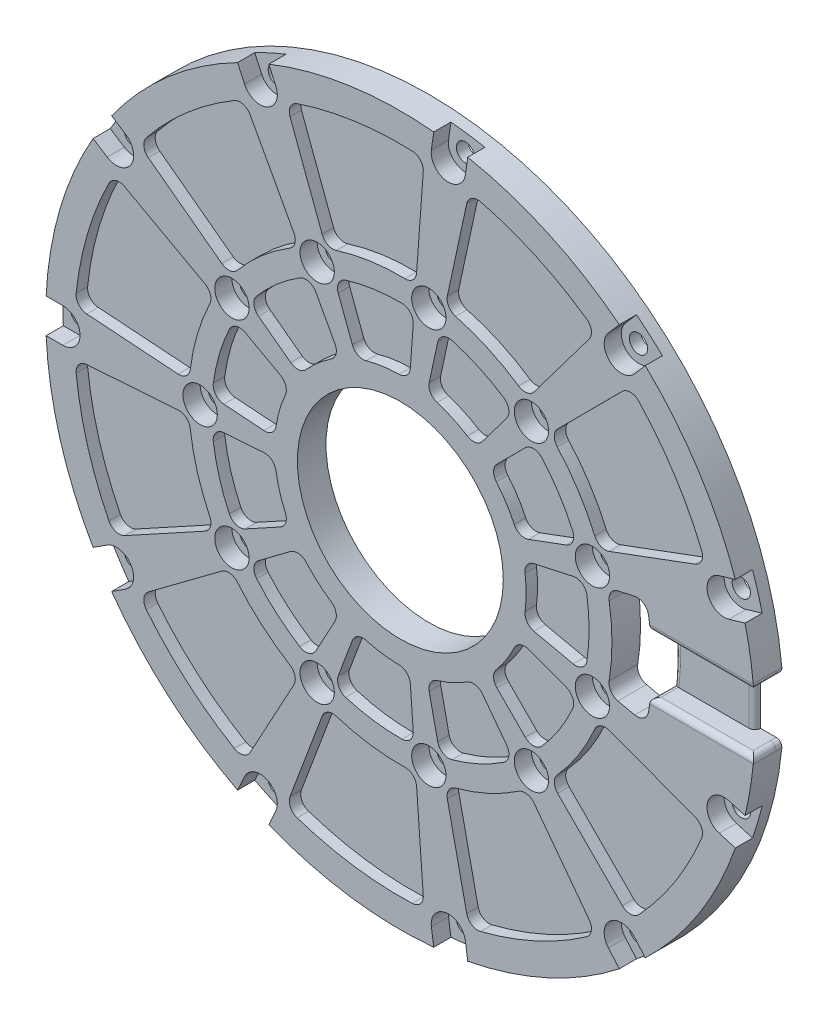
SolidWorks part; units mm, degrees
material "ABS"
ref_plane "Front Plane" through (0, 0, 0) normal (0, 0, 1) x (1, 0, 0)
ref_plane "Top Plane" through (0, 0, 0) normal (0, 1, 0) x (1, 0, 0)
ref_plane "Right Plane" through (0, 0, 0) normal (1, 0, 0) x (0, 0, -1)
sketch "Sketch1" plane through (0, 0, -63.9958) normal (0, 0, 1) x (1, 0, 0)
  circle A0 centre (89.0728, 47.2587) radius 62
  circle A2 centre (89.0728, 47.2587) radius 18
  dimension "D1" = 124
  dimension "D2" = 36
extrude "Boss-Extrude1" add sketch "Sketch1" along normal blind 5
sketch "Sketch2" plane through (0, 0, -58.9958) normal (0, 0, 1) x (1, 0, 0)
  line L0 (89.0728, 47.2587) -> (54.0728, 47.2587) construction
  circle A0 centre (54.0728, 47.2587) radius 1.575
  circle A1 centre (59.6289, 66.1811) radius 1.575
  circle A2 centre (74.5333, 79.0958) radius 1.575
  circle A3 centre (94.0538, 81.9025) radius 1.575
  circle A4 centre (111.9929, 73.7099) radius 1.575
  circle A5 centre (122.655, 57.1193) radius 1.575
  circle A6 centre (122.655, 37.3981) radius 1.575
  circle A7 centre (111.9929, 20.8075) radius 1.575
  circle A8 centre (94.0538, 12.615) radius 1.575
  circle A9 centre (74.5333, 15.4216) radius 1.575
  circle A10 centre (59.6289, 28.3363) radius 1.575
  point P27 (89.0728, 47.2587)
  dimension "D2" = 3.15
  dimension "D3" = 11
  dimension "D1" = 35
extrude "Cut-Extrude1" cut sketch "Sketch2" against normal through all
sketch "Sketch4" plane through (0, 0, -58.9958) normal (0, 0, 1) x (1, 0, 0)
  line L0 (89.0728, 47.2587) -> (30.0728, 47.2587) construction
  circle A0 centre (30.0728, 47.2587) radius 1.6
  circle A1 centre (39.4388, 79.1565) radius 1.6
  circle A2 centre (64.5633, 100.927) radius 1.6
  circle A3 centre (97.4694, 105.6582) radius 1.6
  circle A4 centre (127.7096, 91.8479) radius 1.6
  circle A5 centre (145.6829, 63.8809) radius 1.6
  circle A6 centre (145.6829, 30.6365) radius 1.6
  circle A7 centre (127.7096, 2.6695) radius 1.6
  circle A8 centre (97.4694, -11.1408) radius 1.6
  circle A9 centre (64.5633, -6.4096) radius 1.6
  circle A10 centre (39.4388, 15.3609) radius 1.6
  point P28 (89.0728, 47.2587)
  dimension "D2" = 3.2
  dimension "D1" = 59
  dimension "D3" = 11
extrude "Cut-Extrude3" cut sketch "Sketch4" against normal through all
sketch "Sketch3" plane through (0, 0, -58.9958) normal (0, 0, 1) x (1, 0, 0)
  line L0 (89.0728, 47.2587) -> (94.0538, 81.9025) construction
  line L1 (89.0728, 47.2587) -> (74.5333, 79.0958) construction
  line L2 (78.216, 76.2264) -> (80.6793, 69.654)
  line L3 (91.3287, 78.1118) -> (90.8168, 71.1116)
  line L44 (89.0728, 47.2587) -> (64.5633, 100.927) construction
  line L45 (89.0728, 47.2587) -> (97.4694, 105.6582) construction
  line L46 (75.4037, 83.73) -> (69.7833, 98.7263)
  line L47 (93.0808, 102.076) -> (91.913, 86.1037)
  line L52 (127.1182, 55.5982) -> (130.0522, 56.2414)
  line L53 (130.0522, 38.2761) -> (127.1182, 38.9192)
  line L68 (122.081, 91.207) -> (112.4633, 78.4017)
  line L69 (97.2915, 85.3304) -> (100.6709, 100.9847)
  line L70 (140.6014, 66.3848) -> (125.5873, 60.812)
  line L71 (116.5699, 74.8433) -> (127.8762, 86.1855)
  line L72 (142.7617, 35.4901) -> (127.1182, 38.9192) [skipped]
  line L73 (127.1182, 55.5982) -> (142.7617, 59.0273) [skipped]
  line L74 (127.8762, 8.3319) -> (116.5699, 19.6742)
  line L75 (125.5873, 33.7055) -> (140.6014, 28.1326)
  line L76 (100.6709, -6.4673) -> (97.2915, 9.187)
  line L77 (112.4633, 16.1158) -> (122.081, 3.3104)
  line L78 (69.7833, -4.2089) -> (75.4037, 10.7874)
  line L79 (91.913, 8.4137) -> (93.0808, -7.5586)
  line L80 (45.0199, 14.3901) -> (57.8558, 23.9671)
  line L81 (70.4609, 13.0447) -> (62.8081, -1.0234)
  line L82 (34.2431, 43.4246) -> (50.219, 44.5418)
  line L83 (54.918, 28.5384) -> (40.8742, 20.8409)
  line L84 (40.8742, 73.6765) -> (54.918, 65.979)
  line L85 (50.219, 49.9756) -> (34.2431, 51.0928)
  line L86 (62.8081, 95.5409) -> (70.4609, 81.4727)
  line L87 (57.8558, 70.5503) -> (45.0199, 80.1273)
  line L88 (95.6006, 77.4975) -> (94.1195, 70.6367)
  line L89 (107.651, 71.9943) -> (103.4358, 66.3821)
  line L90 (110.9127, 69.168) -> (105.9575, 64.1971)
  line L91 (118.0748, 58.0235) -> (111.4946, 55.5811)
  line L92 (119.2908, 53.8825) -> (112.4347, 52.3796)
  line L93 (119.2908, 40.635) -> (112.4347, 42.1378)
  line L94 (118.0748, 36.4939) -> (111.4946, 38.9363)
  line L95 (110.9127, 25.3494) -> (105.9575, 30.3204)
  line L96 (107.651, 22.5231) -> (103.4358, 28.1353)
  line L97 (95.6006, 17.0199) -> (94.1195, 23.8807)
  line L98 (91.3287, 16.4057) -> (90.8168, 23.4059)
  line L99 (78.216, 18.291) -> (80.6793, 24.8634)
  line L100 (74.2901, 20.0839) -> (77.6441, 26.2495)
  line L101 (64.2783, 28.7591) -> (69.9039, 32.9565)
  line L102 (61.945, 32.3899) -> (68.1, 35.7634)
  line L103 (58.2127, 45.1008) -> (65.2145, 45.5904)
  line L104 (58.2127, 49.4167) -> (65.2145, 48.927)
  line L105 (61.945, 62.1275) -> (68.1, 58.754)
  line L106 (64.2783, 65.7583) -> (69.9039, 61.5609)
  line L107 (74.2901, 74.4336) -> (77.6441, 68.2679)
  arc A0 (88.843, 69.2575) -> (83.0955, 68.4311) centre (89.0728, 47.2587) ccw
  arc A1 (89.3508, 80.2575) -> (79.5092, 78.8425) centre (89.0728, 47.2587) ccw
  arc A22 (91.3287, 78.1118) -> (89.3508, 80.2575) centre (89.334, 78.2576) ccw
  arc A23 (78.216, 76.2264) -> (79.5092, 78.8425) centre (80.0888, 76.9283) cw
  arc A24 (80.6793, 69.654) -> (83.0955, 68.4311) centre (82.5521, 70.3559) ccw
  arc A25 (90.8168, 71.1116) -> (88.843, 69.2575) centre (88.8222, 71.2574) cw
  arc A86 (77.8815, 82.5256) -> (89.875, 84.25) centre (89.0728, 47.2587) cw
  arc A87 (71.0227, 101.3253) -> (91.1594, 104.2205) centre (89.0728, 47.2587) cw
  arc A88 (91.913, 86.1037) -> (89.875, 84.25) centre (89.9183, 86.2495) cw
  arc A89 (93.0808, 102.076) -> (91.1594, 104.2205) centre (91.0862, 102.2218) ccw
  arc A90 (69.7833, 98.7263) -> (71.0227, 101.3253) centre (71.6561, 99.4282) cw
  arc A91 (75.4037, 83.73) -> (77.8815, 82.5256) centre (77.2765, 84.4319) ccw
  arc A104 (132.4522, 54.6225) -> (132.4522, 39.895) centre (89.0728, 47.2587) cw
  arc A106 (127.1182, 55.5982) -> (125.5734, 53.3171) centre (127.5464, 53.6446) ccw
  arc A107 (125.5734, 53.3171) -> (125.5734, 41.2003) centre (89.0728, 47.2587) cw
  arc A108 (127.1182, 38.9192) -> (125.5734, 41.2003) centre (127.5464, 40.8728) cw
  arc A152 (132.4522, 54.6225) -> (130.0522, 56.2414) centre (130.4804, 54.2877) ccw
  arc A153 (132.4522, 39.895) -> (130.0522, 38.2761) centre (130.4804, 40.2297) cw
  arc A154 (122.081, 91.207) -> (121.624, 94.0499) centre (120.4819, 92.4081) ccw
  arc A155 (103.1187, 102.501) -> (121.624, 94.0499) centre (89.0728, 47.2587) cw
  arc A156 (100.6709, 100.9847) -> (103.1187, 102.501) centre (102.6259, 100.5627) cw
  arc A157 (97.2915, 85.3304) -> (98.7248, 82.9776) centre (99.2465, 84.9084) ccw
  arc A158 (98.7248, 82.9776) -> (109.7466, 77.9441) centre (89.0728, 47.2587) cw
  arc A159 (112.4633, 78.4017) -> (109.7466, 77.9441) centre (110.8641, 79.6028) cw
  arc A160 (140.6014, 66.3848) -> (141.7539, 69.0235) centre (139.9054, 68.2598) ccw
  arc A161 (130.7552, 86.1377) -> (141.7539, 69.0235) centre (89.0728, 47.2587) cw
  arc A162 (127.8762, 86.1855) -> (130.7552, 86.1377) centre (129.2927, 84.7735) cw
  arc A163 (116.5699, 74.8433) -> (116.5036, 72.0891) centre (117.9864, 73.4313) ccw
  arc A164 (116.5036, 72.0891) -> (123.0545, 61.8958) centre (89.0728, 47.2587) cw
  arc A165 (125.5873, 60.812) -> (123.0545, 61.8958) centre (124.8913, 62.687) cw
  arc A166 (142.7617, 35.4901) -> (145.1578, 37.0869) centre (143.19, 37.4438) ccw [skipped]
  arc A167 (145.1578, 57.4306) -> (145.1578, 37.0869) centre (89.0728, 47.2587) cw [skipped]
  arc A168 (142.7617, 59.0273) -> (145.1578, 57.4306) centre (143.19, 57.0737) cw [skipped]
  arc A169 (127.1182, 55.5982) -> (125.5734, 53.3171) centre (127.5464, 53.6446) ccw [skipped]
  arc A170 (125.5734, 53.3171) -> (125.5734, 41.2003) centre (89.0728, 47.2587) cw [skipped]
  arc A171 (127.1182, 38.9192) -> (125.5734, 41.2003) centre (127.5464, 40.8728) cw [skipped]
  arc A172 (127.8762, 8.3319) -> (130.7552, 8.3797) centre (129.2927, 9.7439) ccw
  arc A173 (141.7539, 25.4939) -> (130.7552, 8.3797) centre (89.0728, 47.2587) cw
  arc A174 (140.6014, 28.1326) -> (141.7539, 25.4939) centre (139.9054, 26.2576) cw
  arc A175 (125.5873, 33.7055) -> (123.0545, 32.6216) centre (124.8913, 31.8305) ccw
  arc A176 (123.0545, 32.6216) -> (116.5036, 22.4283) centre (89.0728, 47.2587) cw
  arc A177 (116.5699, 19.6742) -> (116.5036, 22.4283) centre (117.9864, 21.0861) cw
  arc A178 (100.6709, -6.4673) -> (103.1187, -7.9836) centre (102.6259, -6.0453) ccw
  arc A179 (121.624, 0.4675) -> (103.1187, -7.9836) centre (89.0728, 47.2587) cw
  arc A180 (122.081, 3.3104) -> (121.624, 0.4675) centre (120.4819, 2.1093) cw
  arc A181 (112.4633, 16.1158) -> (109.7466, 16.5733) centre (110.8641, 14.9147) ccw
  arc A182 (109.7466, 16.5733) -> (98.7248, 11.5398) centre (89.0728, 47.2587) cw
  arc A183 (97.2915, 9.187) -> (98.7248, 11.5398) centre (99.2465, 9.6091) cw
  arc A184 (69.7833, -4.2089) -> (71.0227, -6.8079) centre (71.6561, -4.9108) ccw
  arc A185 (91.1594, -9.7031) -> (71.0227, -6.8079) centre (89.0728, 47.2587) cw
  arc A186 (93.0808, -7.5586) -> (91.1594, -9.7031) centre (91.0862, -7.7044) cw
  arc A187 (91.913, 8.4137) -> (89.875, 10.2674) centre (89.9183, 8.2679) ccw
  arc A188 (89.875, 10.2674) -> (77.8815, 11.9918) centre (89.0728, 47.2587) cw
  arc A189 (75.4037, 10.7874) -> (77.8815, 11.9918) centre (77.2765, 10.0855) cw
  arc A190 (45.0199, 14.3901) -> (44.6575, 11.5336) centre (46.216, 12.7871) ccw
  arc A191 (60.0323, -1.7887) -> (44.6575, 11.5336) centre (89.0728, 47.2587) cw
  arc A192 (62.8081, -1.0234) -> (60.0323, -1.7887) centre (61.0512, -0.0677) cw
  arc A193 (70.4609, 13.0447) -> (69.7486, 15.706) centre (68.7041, 14.0004) ccw
  arc A194 (69.7486, 15.706) -> (60.5913, 23.6408) centre (89.0728, 47.2587) cw
  arc A195 (57.8558, 23.9671) -> (60.5913, 23.6408) centre (59.0518, 22.3642) cw
  arc A196 (34.2431, 43.4246) -> (32.3938, 41.2175) centre (34.3826, 41.4295) ccw
  arc A197 (38.1253, 21.6979) -> (32.3938, 41.2175) centre (89.0728, 47.2587) cw
  arc A198 (40.8742, 20.8409) -> (38.1253, 21.6979) centre (39.9129, 22.5948) cw
  arc A199 (54.918, 28.5384) -> (55.7576, 31.1623) centre (53.9567, 30.2922) ccw
  arc A200 (55.7576, 31.1623) -> (52.3438, 42.7883) centre (89.0728, 47.2587) cw
  arc A201 (50.219, 44.5418) -> (52.3438, 42.7883) centre (50.3585, 42.5467) cw
  arc A202 (40.8742, 73.6765) -> (38.1253, 72.8195) centre (39.9129, 71.9226) ccw
  arc A203 (32.3938, 53.2999) -> (38.1253, 72.8195) centre (89.0728, 47.2587) cw
  arc A204 (34.2431, 51.0928) -> (32.3938, 53.2999) centre (34.3826, 53.0879) cw
  arc A205 (50.219, 49.9756) -> (52.3438, 51.7291) centre (50.3585, 51.9708) ccw
  arc A206 (52.3438, 51.7291) -> (55.7576, 63.3551) centre (89.0728, 47.2587) cw
  arc A207 (54.918, 65.979) -> (55.7576, 63.3551) centre (53.9567, 64.2252) cw
  arc A208 (62.8081, 95.5409) -> (60.0323, 96.3061) centre (61.0512, 94.5851) ccw
  arc A209 (44.6575, 82.9838) -> (60.0323, 96.3061) centre (89.0728, 47.2587) cw
  arc A210 (45.0199, 80.1273) -> (44.6575, 82.9838) centre (46.216, 81.7303) cw
  arc A211 (57.8558, 70.5503) -> (60.5913, 70.8766) centre (59.0518, 72.1533) ccw
  arc A212 (60.5913, 70.8766) -> (69.7486, 78.8115) centre (89.0728, 47.2587) cw
  arc A213 (70.4609, 81.4727) -> (69.7486, 78.8115) centre (68.7041, 80.517) cw
  arc A214 (107.1472, 74.8688) -> (98.1029, 78.9992) centre (89.0728, 47.2587) ccw
  arc A215 (95.6006, 77.4975) -> (98.1029, 78.9992) centre (97.5556, 77.0755) cw
  arc A216 (100.773, 65.8895) -> (95.491, 68.3017) centre (89.0728, 47.2587) ccw
  arc A217 (94.1195, 70.6367) -> (95.491, 68.3017) centre (96.0745, 70.2147) ccw
  arc A218 (103.4358, 66.3821) -> (100.773, 65.8895) centre (101.8366, 67.5832) cw
  arc A219 (107.651, 71.9943) -> (107.1472, 74.8688) centre (106.0518, 73.1954) ccw
  arc A220 (119.2051, 60.714) -> (113.8296, 69.0785) centre (89.0728, 47.2587) ccw
  arc A221 (110.9127, 69.168) -> (113.8296, 69.0785) centre (112.3292, 67.7561) cw
  arc A222 (108.9882, 56.6063) -> (105.8488, 61.4912) centre (89.0728, 47.2587) ccw
  arc A223 (105.9575, 64.1971) -> (105.8488, 61.4912) centre (107.3739, 62.7851) ccw
  arc A224 (111.4946, 55.5811) -> (108.9882, 56.6063) centre (110.7986, 57.4561) cw
  arc A225 (118.0748, 58.0235) -> (119.2051, 60.714) centre (117.3789, 59.8985) ccw
  arc A226 (121.6962, 42.2873) -> (121.6962, 52.2301) centre (89.0728, 47.2587) ccw
  arc A227 (119.2908, 53.8825) -> (121.6962, 52.2301) centre (119.719, 51.9288) cw
  arc A228 (110.8804, 44.3554) -> (110.8804, 50.162) centre (89.0728, 47.2587) ccw
  arc A229 (112.4347, 52.3796) -> (110.8804, 50.162) centre (112.8629, 50.426) ccw
  arc A230 (112.4347, 42.1378) -> (110.8804, 44.3554) centre (112.8629, 44.0914) cw
  arc A231 (119.2908, 40.635) -> (121.6962, 42.2873) centre (119.719, 42.5886) ccw
  arc A232 (113.8296, 25.4389) -> (119.2051, 33.8034) centre (89.0728, 47.2587) ccw
  arc A233 (118.0748, 36.4939) -> (119.2051, 33.8034) centre (117.3789, 34.6189) cw
  arc A234 (105.8488, 33.0262) -> (108.9882, 37.9111) centre (89.0728, 47.2587) ccw
  arc A235 (111.4946, 38.9363) -> (108.9882, 37.9111) centre (110.7986, 37.0613) ccw
  arc A236 (105.9575, 30.3204) -> (105.8488, 33.0262) centre (107.3739, 31.7323) cw
  arc A237 (110.9127, 25.3494) -> (113.8296, 25.4389) centre (112.3292, 26.7614) ccw
  arc A238 (98.1029, 15.5182) -> (107.1472, 19.6486) centre (89.0728, 47.2587) ccw
  arc A239 (107.651, 22.5231) -> (107.1472, 19.6486) centre (106.0518, 21.322) cw
  arc A240 (95.491, 26.2157) -> (100.773, 28.6279) centre (89.0728, 47.2587) ccw
  arc A241 (103.4358, 28.1353) -> (100.773, 28.6279) centre (101.8366, 26.9342) ccw
  arc A242 (94.1195, 23.8807) -> (95.491, 26.2157) centre (96.0745, 24.3027) cw
  arc A243 (95.6006, 17.0199) -> (98.1029, 15.5182) centre (97.5556, 17.4419) ccw
  arc A244 (79.5092, 15.6749) -> (89.3508, 14.2599) centre (89.0728, 47.2587) ccw
  arc A245 (91.3287, 16.4057) -> (89.3508, 14.2599) centre (89.334, 16.2598) cw
  arc A246 (83.0955, 26.0863) -> (88.843, 25.2599) centre (89.0728, 47.2587) ccw
  arc A247 (90.8168, 23.4059) -> (88.843, 25.2599) centre (88.8222, 23.26) ccw
  arc A248 (80.6793, 24.8634) -> (83.0955, 26.0863) centre (82.5521, 24.1615) cw
  arc A249 (78.216, 18.291) -> (79.5092, 15.6749) centre (80.0888, 17.5891) ccw
  arc A250 (63.9519, 25.8592) -> (71.4662, 19.348) centre (89.0728, 47.2587) ccw
  arc A251 (74.2901, 20.0839) -> (71.4662, 19.348) centre (72.5332, 21.0396) cw
  arc A252 (72.5977, 32.6789) -> (76.9861, 28.8764) centre (89.0728, 47.2587) ccw
  arc A253 (77.6441, 26.2495) -> (76.9861, 28.8764) centre (75.8873, 27.2052) ccw
  arc A254 (69.9039, 32.9565) -> (72.5977, 32.6789) centre (71.0999, 31.3535) cw
  arc A255 (64.2783, 28.7591) -> (63.9519, 25.8592) centre (65.4743, 27.1561) ccw
  arc A256 (56.3703, 42.8377) -> (59.1715, 33.2976) centre (89.0728, 47.2587) ccw
  arc A257 (61.945, 32.3899) -> (59.1715, 33.2976) centre (60.9837, 34.1437) cw
  arc A258 (67.3306, 43.9005) -> (68.9665, 38.3291) centre (89.0728, 47.2587) ccw
  arc A259 (68.1, 35.7634) -> (68.9665, 38.3291) centre (67.1387, 37.5173) ccw
  arc A260 (65.2145, 45.5904) -> (67.3306, 43.9005) centre (65.354, 43.5952) cw
  arc A261 (58.2127, 45.1008) -> (56.3703, 42.8377) centre (58.3522, 43.1056) ccw
  arc A262 (59.1715, 61.2198) -> (56.3703, 51.6797) centre (89.0728, 47.2587) ccw
  arc A263 (58.2127, 49.4167) -> (56.3703, 51.6797) centre (58.3522, 51.4118) cw
  arc A264 (68.9665, 56.1883) -> (67.3306, 50.6169) centre (89.0728, 47.2587) ccw
  arc A265 (65.2145, 48.927) -> (67.3306, 50.6169) centre (65.354, 50.9222) ccw
  arc A266 (68.1, 58.754) -> (68.9665, 56.1883) centre (67.1387, 57.0001) cw
  arc A267 (61.945, 62.1275) -> (59.1715, 61.2198) centre (60.9837, 60.3737) ccw
  arc A268 (71.4662, 75.1694) -> (63.9519, 68.6582) centre (89.0728, 47.2587) ccw
  arc A269 (64.2783, 65.7583) -> (63.9519, 68.6582) centre (65.4743, 67.3613) cw
  arc A270 (76.9861, 65.6411) -> (72.5977, 61.8385) centre (89.0728, 47.2587) ccw
  arc A271 (69.9039, 61.5609) -> (72.5977, 61.8385) centre (71.0999, 63.1639) ccw
  arc A272 (77.6441, 68.2679) -> (76.9861, 65.6411) centre (75.8873, 67.3122) cw
  arc A273 (74.2901, 74.4336) -> (71.4662, 75.1694) centre (72.5332, 73.4779) ccw
  point P52 (89.0728, 47.2587)
  point P142 (89.0728, 47.2587)
  point P291 (89.0728, 47.2587)
  point P293 (89.0728, 47.2587)
  dimension "D1" = 33
  dimension "D2" = 22
  dimension "D5" = 44
  dimension "D6" = 6.5725
  dimension "D7" = 57
  dimension "D8" = 37
  dimension "D11" = 2
  dimension "D12" = 2
  dimension "D13" = 11
  dimension "D14" = 3.0037
  dimension "D10" = 15.9723
  dimension "D4" = 7.0002
  dimension "D3" = 2
  dimension "D15" = 37
  dimension "D16" = 11
  dimension "D9" = 4
extrude "Cut-Extrude2" cut sketch "Sketch3" against normal blind 2
extrude "Cut-Extrude5" cut sketch "Sketch3<3>" against normal through all contours A153 A104 A152 L52 A106 A107 A108 L53 region at (129.3712, 47.2587, -58.9958)
sketch "Sketch3<3>" plane through (0, 0, -58.9958) normal (0, 0, 1) x (1, 0, 0) same geometry as "Sketch3"
sketch "Sketch7" plane through (0, 0, -58.9958) normal (0, 0, 1) x (1, 0, 0)
  line L0 (133.0728, 47.2587) -> (151.0728, 47.2587) construction
  line L1 (132.7878, 52.2587) -> (151.0728, 52.2587)
  line L2 (132.7878, 42.2587) -> (151.0728, 42.2587)
  line L3 (132.7878, 52.2587) -> (132.7878, 42.2587)
  line L4 (151.0728, 47.2587) -> (151.0728, 52.2587)
  line L5 (151.0728, 47.2587) -> (151.0728, 42.2587)
  arc A0 (132.4522, 39.895) -> (132.4522, 54.6225) centre (89.0728, 47.2587) ccw construction
  circle A1 centre (89.0728, 47.2587) radius 62 construction
  dimension "D1" = 5
  dimension "D2" = 5
extrude "Cut-Extrude6" cut sketch "Sketch7" against normal blind 4 contours L4 L1 L3 L2 L5
fillet "Fillet1" radius 1 7 edges at (132.7878, 42.2587, -60.9958) (150.8709, 42.2587, -60.9958) (132.7878, 52.2587, -60.9958) (150.8709, 52.2587, -60.9958) (133.0728, 47.2587, -62.9958) (141.8293, 52.2587, -58.9958) (141.8293, 42.2587, -58.9958)
sketch "Sketch8" plane through (0, 0, -62.9958) normal (0, 0, 1) x (1, 0, 0)
  line L0 (149.777, 52.2587) -> (133.671, 52.2587) construction
  line L1 (155.0728, 42.2587) -> (147.0728, 42.2587)
  line L2 (155.0728, 42.2587) -> (155.0728, 52.2587)
  line L3 (155.0728, 52.2587) -> (147.0728, 52.2587)
  line L4 (147.0728, 42.2587) -> (147.0728, 52.2587)
  line L5 (155.0728, 42.2587) -> (147.0728, 52.2587) construction
  line L6 (155.0728, 52.2587) -> (147.0728, 42.2587) construction
  arc A0 (150.7721, 41.1603) -> (150.7721, 53.3571) centre (89.0728, 47.2587) ccw construction
  point P0 (151.0728, 47.2587)
  dimension "D1" = 8
extrude "Cut-Extrude7" cut sketch "Sketch8" against normal through all
fillet "Fillet2" radius 1 2 edges at (150.8709, 42.2587, -63.4958) (150.8709, 52.2587, -63.4958)
fillet "Fillet3" radius 1 1 edges at (147.0728, 47.2587, -62.9958)
sketch "Sketch10" plane through (0, 0, -58.9958) normal (0, 0, 1) x (1, 0, 0)
  line L0 (30.0728, 44.2587) -> (27.2562, 44.2587)
  line L1 (30.0728, 50.2587) -> (27.2562, 50.2587)
  line L2 (37.8837, 83.722) -> (34.6399, 78.6745)
  line L3 (27.2562, 50.2587) -> (26.2962, 50.2587)
  line L5 (27.2562, 44.2587) -> (26.2962, 44.2587)
  line L6 (26.2962, 50.2587) -> (26.2962, 44.2587)
  line L7 (37.8169, 76.6328) -> (35.4475, 78.1555)
  line L8 (35.4475, 78.1555) -> (34.6399, 78.6745)
  line L9 (41.0608, 81.6803) -> (38.6913, 83.203)
  line L10 (38.6913, 83.203) -> (37.8837, 83.722)
  line L11 (65.7234, 105.6085) -> (60.2656, 103.116)
  line L12 (61.8344, 99.6808) -> (60.6644, 102.2428)
  line L13 (60.6644, 102.2428) -> (60.2656, 103.116)
  line L14 (67.2922, 102.1732) -> (66.1222, 104.7353)
  line L15 (66.1222, 104.7353) -> (65.7234, 105.6085)
  line L16 (100.9763, 108.9694) -> (95.0374, 109.8232)
  line L17 (94.4999, 106.0851) -> (94.9007, 108.873)
  line L18 (94.9007, 108.873) -> (95.0374, 109.8232)
  line L19 (100.4388, 105.2312) -> (100.8397, 108.0191)
  line L20 (100.8397, 108.0191) -> (100.9763, 108.9694)
  line L21 (132.4499, 92.7375) -> (127.9154, 96.6667)
  line L22 (125.4423, 93.8125) -> (127.2868, 95.9411)
  line L23 (127.2868, 95.9411) -> (127.9154, 96.6667)
  line L24 (129.9768, 89.8834) -> (131.8213, 92.012)
  line L25 (131.8213, 92.012) -> (132.4499, 92.7375)
  line L26 (150.1517, 62.0664) -> (148.4613, 67.8234)
  line L27 (144.8377, 66.7594) -> (147.5402, 67.5529)
  line L28 (147.5402, 67.5529) -> (148.4613, 67.8234)
  line L29 (146.5281, 61.0025) -> (149.2305, 61.796)
  line L30 (149.2305, 61.796) -> (150.1517, 62.0664)
  line L31 (148.4613, 26.694) -> (150.1517, 32.451)
  line L32 (146.5281, 33.515) -> (149.2305, 32.7214)
  line L33 (149.2305, 32.7214) -> (150.1517, 32.451)
  line L34 (144.8377, 27.758) -> (147.5402, 26.9645)
  line L35 (147.5402, 26.9645) -> (148.4613, 26.694)
  line L36 (127.9154, -2.1492) -> (132.4499, 1.7799)
  line L37 (129.9768, 4.6341) -> (131.8213, 2.5054)
  line L38 (131.8213, 2.5054) -> (132.4499, 1.7799)
  line L39 (125.4423, 0.7049) -> (127.2868, -1.4237)
  line L40 (127.2868, -1.4237) -> (127.9154, -2.1492)
  line L41 (95.0374, -15.3058) -> (100.9763, -14.4519)
  line L42 (100.4388, -10.7138) -> (100.8397, -13.5017)
  line L43 (100.8397, -13.5017) -> (100.9763, -14.4519)
  line L44 (94.4999, -11.5677) -> (94.9007, -14.3556)
  line L45 (94.9007, -14.3556) -> (95.0374, -15.3058)
  line L46 (60.2656, -8.5986) -> (65.7234, -11.0911)
  line L47 (67.2922, -7.6558) -> (66.1222, -10.2179)
  line L48 (66.1222, -10.2179) -> (65.7234, -11.0911)
  line L49 (61.8344, -5.1633) -> (60.6644, -7.7254)
  line L50 (60.6644, -7.7254) -> (60.2656, -8.5986)
  line L51 (34.6399, 15.8429) -> (37.8837, 10.7954)
  line L52 (41.0608, 12.8371) -> (38.6913, 11.3144)
  line L53 (38.6913, 11.3144) -> (37.8837, 10.7954)
  line L54 (37.8169, 17.8847) -> (35.4475, 16.3619)
  line L55 (35.4475, 16.3619) -> (34.6399, 15.8429)
  circle A0 centre (54.0728, 47.2587) radius 3
  arc A1 (30.0728, 44.2587) -> (30.0728, 50.2587) centre (30.0728, 47.2587) ccw
  arc A2 (37.8169, 76.6328) -> (41.0608, 81.6803) centre (39.4388, 79.1565) ccw
  circle A3 centre (59.6289, 66.1811) radius 3
  arc A4 (61.8344, 99.6808) -> (67.2922, 102.1732) centre (64.5633, 100.927) ccw
  circle A5 centre (74.5333, 79.0958) radius 3
  arc A6 (94.4999, 106.0851) -> (100.4388, 105.2312) centre (97.4694, 105.6582) ccw
  circle A7 centre (94.0538, 81.9025) radius 3
  arc A8 (125.4423, 93.8125) -> (129.9768, 89.8834) centre (127.7096, 91.8479) ccw
  circle A9 centre (111.9929, 73.7099) radius 3
  arc A10 (144.8377, 66.7594) -> (146.5281, 61.0025) centre (145.6829, 63.8809) ccw
  circle A11 centre (122.655, 57.1193) radius 3
  arc A12 (146.5281, 33.515) -> (144.8377, 27.758) centre (145.6829, 30.6365) ccw
  circle A13 centre (122.655, 37.3981) radius 3
  arc A14 (129.9768, 4.6341) -> (125.4423, 0.7049) centre (127.7096, 2.6695) ccw
  circle A15 centre (111.9929, 20.8075) radius 3
  arc A16 (100.4388, -10.7138) -> (94.4999, -11.5677) centre (97.4694, -11.1408) ccw
  circle A17 centre (94.0538, 12.615) radius 3
  arc A18 (67.2922, -7.6558) -> (61.8344, -5.1633) centre (64.5633, -6.4096) ccw
  circle A19 centre (74.5333, 15.4216) radius 3
  arc A20 (41.0608, 12.8371) -> (37.8169, 17.8847) centre (39.4388, 15.3609) ccw
  circle A21 centre (59.6289, 28.3363) radius 3
  point P103 (89.0728, 47.2587)
  dimension "D1" = 6
  dimension "D2" = 6
  dimension "D3" = 11
extrude "Cut-Extrude8" cut sketch "Sketch10" against normal blind 3
equation "\"HousingIn\"=113"
equation "\"HousingOut\"=124"
equation "\"FrontCutout\"=36"
equation "\"D1@Sketch1\"=\"HousingOut\""
equation "\"D2@Sketch1\"=\"FrontCutout\""
equation "\"D1@Sketch4\"=\"HousingOut\"/2 -3"
